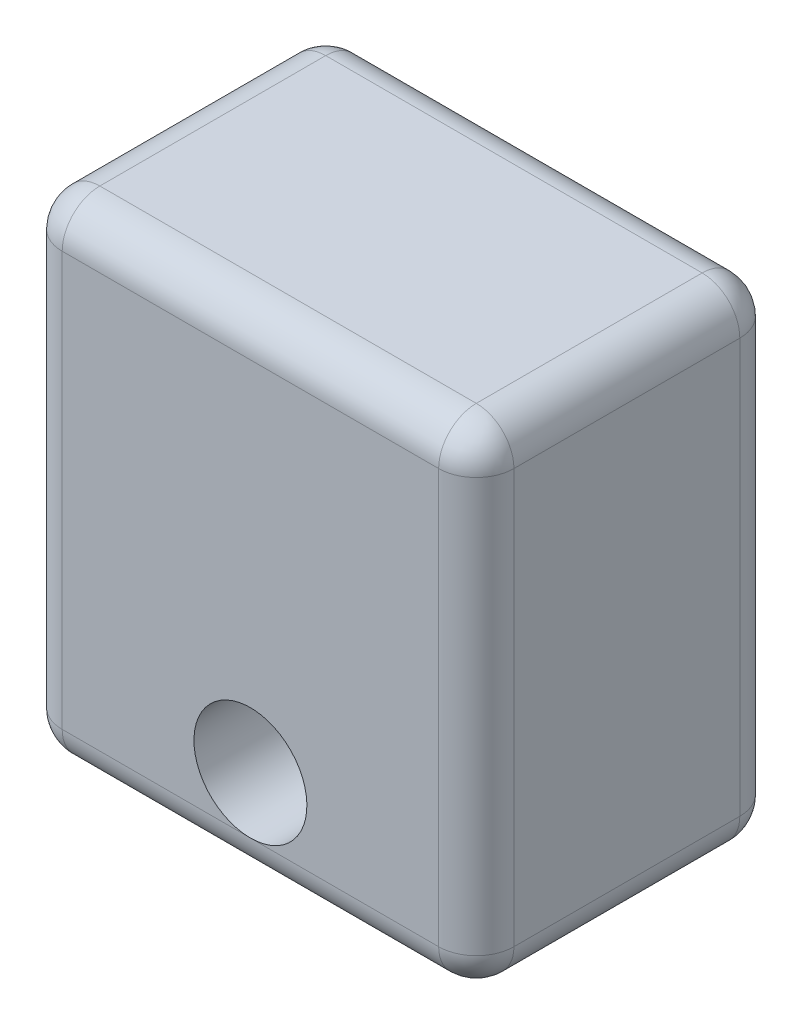
SolidWorks part; units mm, degrees
material "6061-T6 (SS)"
ref_plane "Front Plane" through (0, 0, 0) normal (0, 0, 1) x (1, 0, 0)
ref_plane "Top Plane" through (0, 0, 0) normal (0, 1, 0) x (1, 0, 0)
ref_plane "Right Plane" through (0, 0, 0) normal (1, 0, 0) x (0, 0, -1)
sketch "Sketch1" plane through (0, 0, 0) normal (0, 0, 1) x (1, 0, 0)
  line L1 (-38.1, -22.225) -> (38.1, -22.225)
  line L2 (-38.1, -22.225) -> (-38.1, 60.325)
  line L3 (-38.1, 60.325) -> (38.1, 60.325)
  line L4 (38.1, -22.225) -> (38.1, 60.325)
  line L5 (-38.1, -22.225) -> (38.1, 60.325) construction
  line L6 (-38.1, 60.325) -> (38.1, -22.225) construction
  circle A0 centre (0, -6.35) radius 9.525
  point P0 (0, 19.05)
  dimension "D1" = 19.05
  dimension "D2" = 76.2
  dimension "D3" = 82.55
  dimension "D4" = 15.875
  dimension "D5" = 6.35
extrude "Boss-Extrude1" add sketch "Sketch1" along normal mid plane 50.8
sketch "Sketch2" plane through (-38.1, 0, 0) normal (-1, 0, 0) x (0, 0, 1)
  circle A0 centre (0, 44.45) radius 9.525
  dimension "D2" = 19.05
  dimension "D1" = 44.45
extrude "Cut-Extrude1" cut sketch "Sketch2" against normal blind 50.8
fillet "Fillet1" radius 6.35 12 edges at (-38.1, -22.225, 0) (0, -22.225, 25.4) (38.1, -22.225, 0) (0, -22.225, -25.4) (38.1, 60.325, 0) (0, 60.325, 25.4) (-38.1, 60.325, 0) (0, 60.325, -25.4) (-38.1, 19.05, -25.4) (-38.1, 19.05, 25.4) (38.1, 19.05, 25.4) (38.1, 19.05, -25.4)
